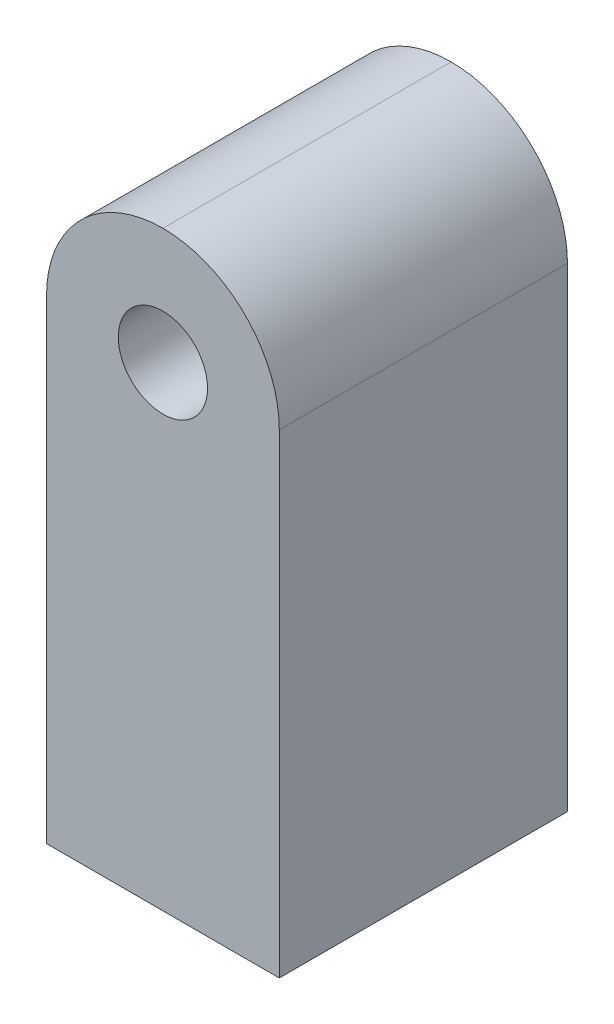
SolidWorks part; units mm, degrees
ref_plane "Front Plane" through (0, 0, 0) normal (0, 0, 1) x (1, 0, 0)
ref_plane "Top Plane" through (0, 0, 0) normal (0, 1, 0) x (1, 0, 0)
ref_plane "Right Plane" through (0, 0, 0) normal (1, 0, 0) x (0, 0, -1)
sketch "Sketch1" plane through (0, 0, 0) normal (0, 0, 1) x (1, 0, 0)
  line L1 (0, 0) -> (40, 0)
  line L2 (0, 0) -> (0, 101.6)
  line L3 (0, 101.6) -> (40, 101.6)
  line L4 (40, 0) -> (40, 101.6)
  dimension "D1" = 40
  dimension "D2" = 101.6
extrude "Boss-Extrude1" add sketch "Sketch1" along normal blind 49.53
fillet "Fillet1" radius 20 2 edges at (40, 101.6, 24.765) (0, 101.6, 24.765)
sketch "Sketch2" plane through (0, 0, 0) normal (0, 0, 1) x (1, 0, 0)
  circle A0 centre (20, 81.6) radius 7.67
  dimension "D1" = 15.34
extrude "Cut-Extrude2" cut sketch "Sketch2" against normal through all and the other way through all
